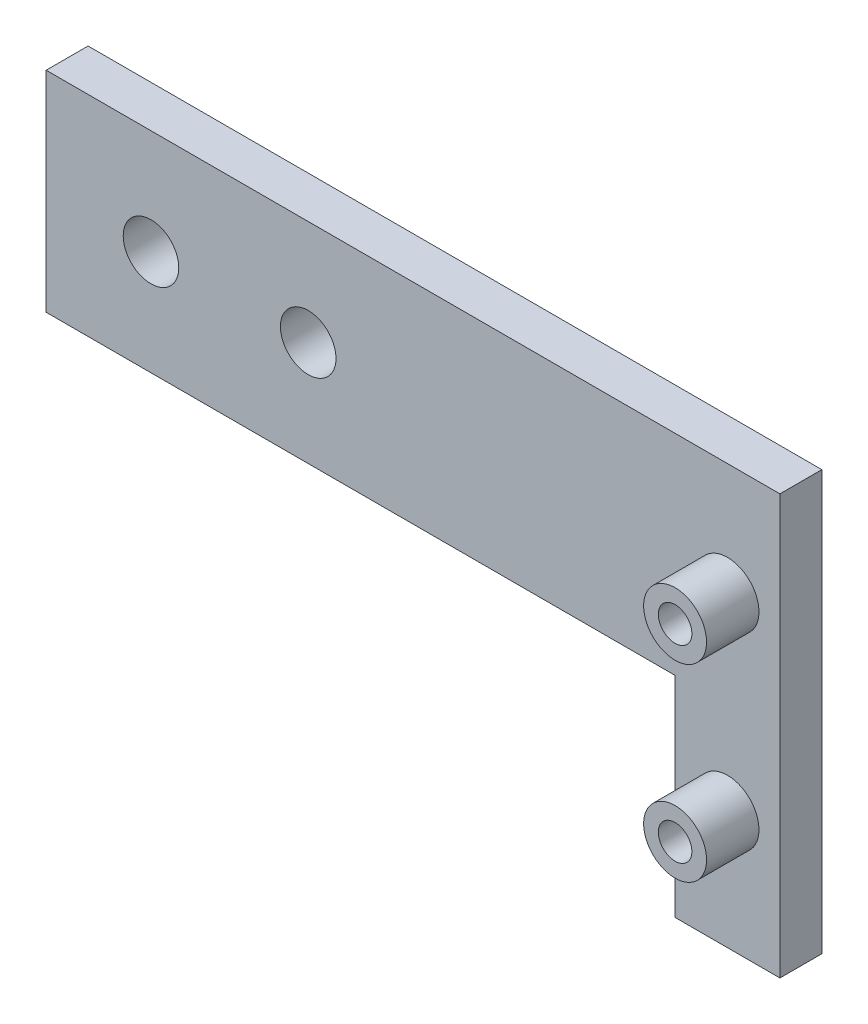
SolidWorks part; units mm, degrees
ref_plane "Front Plane" through (0, 0, 0) normal (0, 0, 1) x (1, 0, 0)
ref_plane "Top Plane" through (0, 0, 0) normal (0, 1, 0) x (1, 0, 0)
ref_plane "Right Plane" through (0, 0, 0) normal (1, 0, 0) x (0, 0, -1)
sketch "Sketch1" plane through (0, 0, 0) normal (0, 0, 1) x (1, 0, 0)
  line L0 (0, 0) -> (0, 35.2)
  line L1 (0, 0) -> (-40.2961, 0)
  line L2 (-40.2961, 0) -> (-40.2961, 35.2)
  line L3 (0, 35.2) -> (-40.2961, 35.2)
  line L4 (-20, 8.45) -> (-20, 0)
  line L5 (-20, 8.45) -> (-40.2961, 8.45)
  line L6 (-20, 26.45) -> (-40.2961, 26.45)
  line L7 (-20, 26.45) -> (-20, 35.2)
  line L8 (-20, 8.45) -> (-20, -2.8)
  line L9 (-20, -2.8) -> (-20, 37.2)
  line L11 (-25, 37.2) -> (-15, 37.2)
  line L12 (-25, 37.2) -> (-25, -2.8)
  line L13 (-25, -2.8) -> (-15, -2.8)
  line L14 (-15, 37.2) -> (-15, -2.8)
  line L15 (-40, 37.2) -> (0, 37.2)
  line L16 (-40, 37.2) -> (-40, 17.2)
  line L17 (-40, 17.2) -> (0, 17.2)
  line L18 (0, 37.2) -> (0, 17.2)
  circle A0 centre (-20, 26.45) radius 1.6
  circle A1 centre (-20, 8.45) radius 1.6
  dimension "D8" = 3.2
  dimension "D1" = 20.2961
  dimension "D2" = 8.45
  dimension "D3" = 20.2961
  dimension "D4" = 8.75
  dimension "D5" = 18
  dimension "D6" = 40.2961
  dimension "D7" = 0
  dimension "D9" = 11.25
  dimension "D10" = 40
  dimension "D11" = 40
  dimension "D12" = 10
  dimension "D13" = 5
  dimension "D14" = 20
  dimension "D15" = 0
  dimension "D16" = 20
  dimension "D17" = 40
extrude "Boss-Extrude1" add sketch "Sketch1" along normal blind 4 contours A1 L9 L1 L14 L17 | A1 L9 L17 L12 L5 | A1 L5 L12 L1 L9 | L12 L13 L8 L1 | L14 L1 L8 L13 | A0 L9 L17 L14 L3 | A0 L6 L12 L17 L9 | A0 L9 L3 L12 L6 | L14 L11 L9 L3 | L11 L12 L3 L9 | L18 L15 L14 L3 | L15 L16 L3 L12 | L3 L16 L6 L12 | L16 L17 L12 L6 | L14 L17 L0 L3 region at (-7.5, 26.2, 0) region at (-17.5, -1.4, 0) region at (-17.4107, 8.6074, 0) region at (-7.5, 36.2, 0) region at (-17.4148, 26.1883, 0) region at (-22.5, -1.4, 0) region at (-22.591, 4.0478, 0) region at (-17.5, 36.2, 0) region at (-22.5828, 21.6457, 0) region at (-22.5877, 13.003, 0) region at (-22.5877, 31.003, 0) region at (-22.5, 36.2, 0) region at (-32.5, 21.825, 0) region at (-32.5, 30.825, 0) region at (-32.5, 36.2, 0)
sketch "Sketch2" plane through (0, 0, 4) normal (0, 0, 1) x (1, 0, 0)
  line L0 (-5, 27.2) -> (-35, 27.2)
  line L1 (0, 17.2) -> (0, 37.2) construction
  line L2 (-40, 37.2) -> (0, 37.2) construction
  circle A0 centre (-35, 27.2) radius 2.5
  circle A1 centre (-5, 27.2) radius 2.5
  dimension "D3" = 5
  dimension "D4" = 5
  dimension "D1" = 30
  dimension "D2" = 5
  dimension "D5" = 10
extrude "Cut-Extrude1" cut sketch "Sketch2" against normal blind 13 contours A0 | A1 region at (-37.4293, 27.2, 4) region at (-5, 29.6293, 4)
sketch "Sketch3" plane through (0, 0, 4) normal (0, 0, 1) x (1, 0, 0)
  circle A0 centre (-20, 26.45) radius 3
  circle A1 centre (-20, 8.45) radius 3
  circle A2 centre (-20, 26.45) radius 1.6
  circle A3 centre (-20, 8.45) radius 1.6
  dimension "D1" = 6
  dimension "D2" = 6
  dimension "D3" = 3.2
  dimension "D4" = 3.2
extrude "Boss-Extrude2" add sketch "Sketch3" along normal blind 5
sketch "Sketch4" plane through (0, 0, 0) normal (0, 0, -1) x (-1, 0, 0)
  circle A0 centre (20, 26.45) radius 2.5
  circle A1 centre (20, 8.45) radius 2.5
  dimension "D1" = 5
  dimension "D2" = 5
extrude "Cut-Extrude3" cut sketch "Sketch4" against normal blind 3
sketch "Sketch5" plane through (0, 0, 4) normal (0, 0, 1) x (1, 0, 0)
  line L1 (0, 37.2) -> (45, 37.2)
  line L2 (0, 37.2) -> (0, 17.2)
  line L3 (0, 17.2) -> (45, 17.2)
  line L4 (45, 37.2) -> (45, 17.2)
  circle A0 centre (20, 27.2) radius 2.65
  circle A1 centre (35, 27.2) radius 2.65
  dimension "D3" = 5.3
  dimension "D4" = 5.3
  dimension "D5" = 10
  dimension "D6" = 15
  dimension "D8" = 10
  dimension "D1" = 45
  dimension "D2" = 20
  dimension "D7" = 10
extrude "Boss-Extrude3" add sketch "Sketch5" against normal up to surface (4 mm away) up to face at (-22.5, 26.45, 0)
sketch "Sketch6" plane through (0, 0, 4) normal (0, 0, 1) x (1, 0, 0)
  line L1 (-40, 37.2) -> (-25, 37.2)
  line L2 (-40, 37.2) -> (-40, 17.2)
  line L3 (-40, 17.2) -> (-25, 17.2)
  line L4 (-25, 37.2) -> (-25, 17.2)
sketch "Sketch7" plane through (0, 0, 4) normal (0, 0, 1) x (1, 0, 0)
  circle A0 centre (-5, 27.2) radius 3
  dimension "D1" = 6
extrude "Boss-Extrude4" add sketch "Sketch7" against normal up to surface (4 mm away) up to face at (-22.5, 26.45, 0)
ref_plane "Plane1" through (-20, 0, 0) normal (1, 0, 0) x (0, 0, -1)
mirror "Mirror1" about plane through (-20, 0, 0) normal (1, 0, 0) of "Boss-Extrude4"
mirror "Mirror2" about plane through (-20, 0, 0) normal (1, 0, 0) of "Boss-Extrude3"
sketch "Sketch8" plane through (0, 0, 4) normal (0, 0, 1) x (1, 0, 0)
  line L0 (-85, 37.2) -> (45, 37.2) construction
  line L1 (45, 17.2) -> (-15, 17.2)
  line L2 (45, 17.2) -> (45, 37.2)
  line L3 (45, 37.2) -> (-15, 37.2)
  line L4 (-15, 17.2) -> (-15, 37.2)
  line L5 (-15, 17.2) -> (-15, -2.8) construction
  dimension "D1" = 0
extrude "Cut-Extrude5" cut sketch "Sketch8" against normal blind 10
